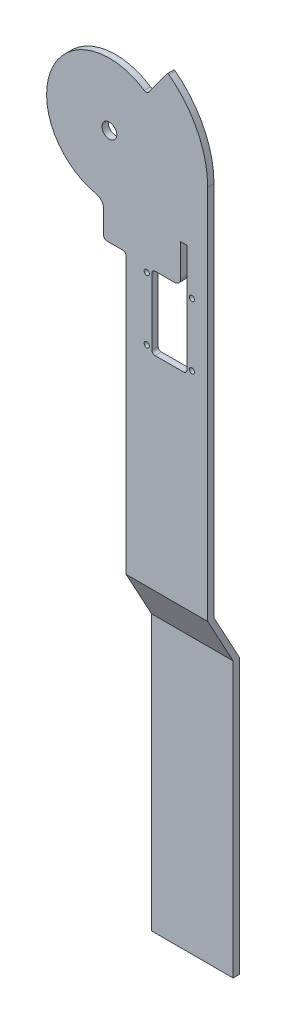
SolidWorks part; units mm, degrees
ref_plane "Front Plane" through (0, 0, 0) normal (0, 0, 1) x (1, 0, 0)
ref_plane "Top Plane" through (0, 0, 0) normal (0, 1, 0) x (1, 0, 0)
ref_plane "Right Plane" through (0, 0, 0) normal (1, 0, 0) x (0, 0, -1)
sketch "Sketch1" plane through (0, 0, 0) normal (0, 0, 1) x (1, 0, 0)
  line L0 (0, 25.4) -> (0, 39.7545) construction
  line L1 (0, 0) -> (1.7777, 2.4073)
  line L2 (39.7545, 0) -> (39.7545, -152.0477)
  line L3 (15.8251, 21.4299) -> (23.3121, 31.5685)
  line L4 (-1.0418, -39.1749) -> (5.4933, -39.1749)
  line L5 (-2.3118, -28.5613) -> (-2.3118, -37.9049)
  line L6 (6.7633, -40.4449) -> (6.7633, -152.0477)
  line L7 (6.7633, -152.0477) -> (39.7545, -152.0477)
  line L8 (31.3336, -24.4667) -> (28.8193, -24.4667) construction
  line L9 (28.8193, -24.4667) -> (28.8193, -27.3837) construction
  line L10 (28.8193, -27.3837) -> (28.8193, -24.4667)
  line L11 (28.8193, -24.4667) -> (31.3336, -24.4667)
  line L12 (31.3336, -24.4667) -> (31.3336, -68.2787)
  line L13 (30.0636, -69.5487) -> (18.4197, -69.5487)
  line L14 (17.1497, -68.2787) -> (17.1497, -41.2786)
  line L15 (18.4197, -40.0086) -> (26.2793, -40.0086)
  line L16 (28.8193, -37.4686) -> (28.8193, -27.3837)
  line L17 (28.8193, -27.3797) -> (27.5575, -27.3797)
  line L18 (27.1203, -29.0635) -> (25.8608, -28.9876)
  line L19 (24.2417, -69.5487) -> (24.2417, -36.019) construction
  line L21 (25.3231, -30.6421) -> (24.0704, -30.4906)
  line L22 (23.4342, -32.1098) -> (22.1929, -31.8832)
  line L23 (21.4604, -33.4611) -> (20.2351, -33.1603)
  line L24 (19.409, -34.6913) -> (18.2039, -34.3173)
  line L25 (17.2873, -35.7959) -> (16.1069, -35.3501)
  line L26 (15.1029, -36.7709) -> (13.9515, -36.2549)
  line L27 (12.8639, -37.6127) -> (11.7456, -37.0284)
  line L28 (10.5783, -38.3184) -> (9.4971, -37.6678)
  line L29 (8.2544, -38.8852) -> (7.2143, -38.1709)
  line L30 (5.9006, -39.3113) -> (4.9054, -38.5357) construction
  line L31 (3.5254, -39.5951) -> (2.5787, -38.761) construction
  line L32 (1.1375, -39.7354) -> (0.2426, -38.8459) construction
  line L33 (-1.2545, -39.7319) -> (-2.0943, -38.7902) construction
  line L34 (-3.642, -39.5845) -> (-4.4236, -38.594)
  line L35 (-6.0163, -39.2938) -> (-6.7369, -38.258)
  line L36 (-8.3689, -38.8608) -> (-9.0259, -37.7835)
  line L37 (-10.6911, -38.287) -> (-11.2821, -37.1723)
  line L38 (-12.9746, -37.5747) -> (-13.4975, -36.4264)
  line L39 (-15.2111, -36.7263) -> (-15.664, -35.5486)
  line L40 (-17.3926, -35.7449) -> (-17.7738, -34.5421)
  line L41 (-19.5111, -34.634) -> (-19.8193, -33.4105)
  line L42 (-21.5589, -33.3978) -> (-21.7929, -32.1579)
  line L43 (-23.5286, -32.0406) -> (-23.6877, -30.7889)
  line L44 (-25.4132, -30.5674) -> (-25.4967, -29.3084)
  line L45 (-27.2057, -28.9835) -> (-27.2133, -27.7218)
  line L46 (-28.8998, -27.2947) -> (-28.8315, -26.0348)
  line L47 (-30.4892, -25.507) -> (-30.3452, -24.2535)
  line L48 (-31.9681, -23.627) -> (-31.749, -22.3844)
  line L49 (27.1203, -29.0635) -> (27.5575, -27.3797)
  line L50 (25.3231, -30.6421) -> (25.8608, -28.9876)
  line L51 (23.4342, -32.1098) -> (24.0704, -30.4906)
  line L52 (21.4604, -33.4611) -> (22.1929, -31.8832)
  line L53 (19.409, -34.6913) -> (20.2351, -33.1603)
  line L54 (17.2873, -35.7959) -> (18.2039, -34.3173)
  line L55 (15.1029, -36.7709) -> (16.1069, -35.3501)
  line L56 (12.8639, -37.6127) -> (13.9515, -36.2549)
  line L57 (10.5783, -38.3184) -> (11.7456, -37.0284)
  line L58 (8.2544, -38.8852) -> (9.4971, -37.6678)
  line L59 (5.9006, -39.3113) -> (7.2143, -38.1709) construction
  line L60 (3.5254, -39.5951) -> (4.9054, -38.5357) construction
  line L61 (1.1375, -39.7354) -> (2.5787, -38.761) construction
  line L62 (-1.2545, -39.7319) -> (0.2426, -38.8459) construction
  line L63 (-3.642, -39.5845) -> (-2.0943, -38.7902)
  line L64 (-6.0163, -39.2938) -> (-4.4236, -38.594)
  line L65 (-8.3689, -38.8608) -> (-6.7369, -38.258)
  line L66 (-10.6911, -38.287) -> (-9.0259, -37.7835)
  line L67 (-12.9746, -37.5747) -> (-11.2821, -37.1723)
  line L68 (-15.2111, -36.7263) -> (-13.4975, -36.4264)
  line L69 (-17.3926, -35.7449) -> (-15.664, -35.5486)
  line L70 (-19.5111, -34.634) -> (-17.7738, -34.5421)
  line L71 (-21.5589, -33.3978) -> (-19.8193, -33.4105)
  line L72 (-23.5286, -32.0406) -> (-21.7929, -32.1579)
  line L73 (-25.4132, -30.5674) -> (-23.6877, -30.7889)
  line L74 (-27.2057, -28.9835) -> (-25.4967, -29.3084)
  line L75 (-28.8998, -27.2947) -> (-27.2133, -27.7218)
  line L76 (-30.4892, -25.507) -> (-28.8315, -26.0348)
  line L77 (-31.9681, -23.627) -> (-30.3452, -24.2535)
  line L78 (-33.3314, -21.6614) -> (-31.749, -22.3844)
  line L80 (-3.7197, 30.3774) -> (-3.7197, 39.5801) construction
  line L81 (3.7197, 30.3774) -> (3.7197, 39.5801) construction
  line L85 (23.2589, -152.0477) -> (23.2589, -179.855) construction
  line L86 (-16.5028, 39.7545) -> (16.4883, 39.7545) construction
  line L87 (-16.5028, 36.1673) -> (-16.5028, 75.7042) construction
  line L88 (0, 39.7545) -> (0, 75.7042) construction
  line L89 (-16.5028, 68.1963) -> (0, 68.1963) construction
  arc A0 (14.0986, 21.1279) -> (-5.3233, -24.8359) centre (0, 0) ccw
  circle A1 centre (0, 0) radius 39.7545 construction
  circle A2 centre (0, 0) radius 32.5772 construction
  circle A3 centre (0, 0) radius 2.9925
  arc A4 (24.0278, 31.6715) -> (39.7545, 0) centre (0, 0) cw
  circle A5 centre (11.7683, 30.3774) radius 1.27 construction
  circle A6 centre (17.1497, 27.6977) radius 1.27 construction
  circle A7 centre (21.9471, 24.0749) radius 1.27 construction
  circle A8 centre (25.9972, 19.6322) radius 1.27 construction
  circle A9 centre (29.1619, 14.5209) radius 1.27 construction
  circle A10 centre (31.3336, 8.9152) radius 1.27 construction
  circle A11 centre (32.4383, 3.0058) radius 1.27 construction
  circle A12 centre (32.4383, -3.0058) radius 1.27 construction
  circle A13 centre (31.3336, -8.9152) radius 1.27 construction
  circle A14 centre (29.1619, -14.5209) radius 1.27 construction
  arc A15 (23.3121, 31.5685) -> (24.0278, 31.6715) centre (23.7208, 31.2668) cw
  arc A16 (5.4933, -39.1749) -> (6.7633, -40.4449) centre (5.4933, -40.4449) cw
  arc A17 (-1.0418, -39.1749) -> (-2.3118, -37.9049) centre (-1.0418, -37.9049) cw
  arc A18 (-2.3118, -28.5613) -> (-5.3233, -24.8359) centre (-6.1218, -28.5613) ccw
  arc A19 (14.0986, 21.1279) -> (15.8251, 21.4299) centre (14.8035, 22.1843) ccw
  arc A20 (-3.7197, 30.3774) -> (3.7197, 30.3774) centre (0, 30.3774) ccw construction
  circle A21 centre (15.1029, -42.0977) radius 1.0427
  circle A22 centre (-11.7683, -30.3774) radius 1.27 construction
  circle A23 centre (-17.1497, -27.6977) radius 1.27 construction
  circle A24 centre (-21.9471, -24.0749) radius 1.27 construction
  circle A25 centre (-25.9972, -19.6322) radius 1.27 construction
  circle A26 centre (-29.1619, -14.5209) radius 1.27 construction
  circle A27 centre (-31.3336, -8.9152) radius 1.27 construction
  circle A28 centre (-32.4383, -3.0058) radius 1.27 construction
  circle A29 centre (-32.4383, 3.0058) radius 1.27 construction
  circle A30 centre (-31.3336, 8.9152) radius 1.27 construction
  circle A31 centre (-29.1619, 14.5209) radius 1.27 construction
  circle A32 centre (-25.9972, 19.6322) radius 1.27 construction
  circle A33 centre (-21.9471, 24.0749) radius 1.27 construction
  circle A34 centre (-17.1497, 27.6977) radius 1.27 construction
  circle A35 centre (-11.7683, 30.3774) radius 1.27 construction
  circle A36 centre (33.3804, -42.0977) radius 1.0427
  circle A37 centre (33.3804, -67.4596) radius 1.0427
  circle A38 centre (15.1029, -67.4596) radius 1.0427
  circle A39 centre (0, 32.5772) radius 2.9925 construction
  circle A40 centre (-8.2514, 57.4535) radius 2.9925 construction
  arc A41 (26.2793, -40.0086) -> (28.8193, -37.4686) centre (26.2793, -37.4686) ccw
  arc A42 (30.0636, -69.5487) -> (31.3336, -68.2787) centre (30.0636, -68.2787) ccw
  arc A43 (18.4197, -69.5487) -> (17.1497, -68.2787) centre (18.4197, -68.2787) cw
  arc A44 (17.1497, -41.2786) -> (18.4197, -40.0086) centre (18.4197, -41.2786) cw
  point P34 (23.6158, 31.9798)
  point P47 (6.7633, -39.1749)
  point P78 (0, 0)
  point P152 (0, 0)
  point P211 (0, 0)
  dimension "D1" = 0.508
  dimension "D2" = 1.27
  dimension "D3" = 3.81
  dimension "D4" = 1.27
  dimension "D5" = 1.27
  dimension "D8" = 2.54
  dimension "D9" = 1.27
  dimension "D6" = 30
  dimension "D7" = 30
extrude "Boss-Extrude4" add sketch "Sketch1" along normal mid plane 2.54 contours A19 A0 A18 L5 A17 L4 A16 L6 L7 L2 A4 A15 L3 A36 A21 A3 L10 L11 L12 L13 L14 L15 L16 region at (16.6619, -51.8162, 0)
sketch "Sketch3" plane through (39.7545, 0, 0) normal (1, 0, 0) x (0, 0, -1)
  line L0 (-1.27, -152.0477) -> (1.27, -152.0477) construction
  line L1 (-1.27, -152.0477) -> (1.27, -152.0477)
  line L2 (-1.27, -152.0477) -> (9.0092, -170.9865)
  line L3 (1.27, -152.0477) -> (11.5492, -170.9865)
  line L4 (9.0092, -170.9865) -> (9.0092, -282.0709)
  line L5 (11.5492, -170.9865) -> (11.5492, -282.0709)
  line L6 (11.5492, -282.0709) -> (9.0092, -282.0709)
extrude "Boss-Extrude5" add sketch "Sketch3" against normal up to vertex (32.9912 mm away) up to point (6.7633, -152.0477, 1.27)
